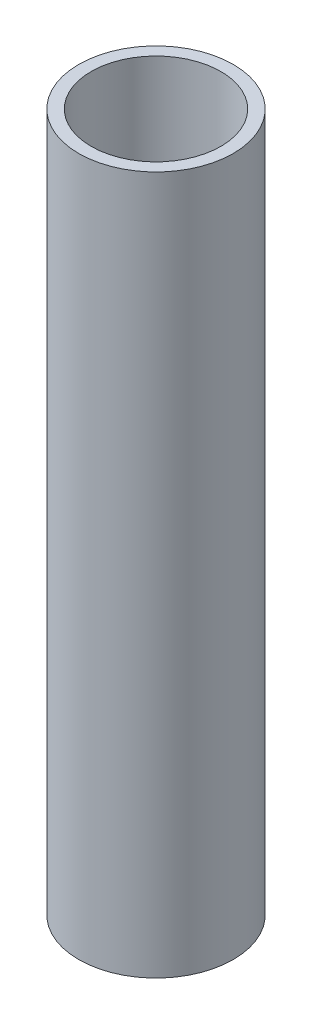
SolidWorks part; units mm, degrees
ref_plane "Front Plane" through (0, 0, 0) normal (0, 0, 1) x (1, 0, 0)
ref_plane "Top Plane" through (0, 0, 0) normal (0, 1, 0) x (1, 0, 0)
ref_plane "Right Plane" through (0, 0, 0) normal (1, 0, 0) x (0, 0, -1)
sketch "Sketch1" plane through (0, 0, 0) normal (0, 1, 0) x (1, 0, 0)
  circle A0 centre (0, 0) radius 12.5
  circle A1 centre (0, 0) radius 10.5
  dimension "D1" = 25
  dimension "D2" = 21
extrude "Boss-Extrude1" add sketch "Sketch1" along normal blind 113
equation "\"cf_tube_outer_diameter\"= 25mm"
equation "\"cf_tube_inner_diameter\" = 21mm"
equation "\"mid_plate_mid_to_top\" = 100mm"
equation "\"mid_plate_mid_to_bottom\" = 30mm"
equation "\"mid_plate_horizontal_spacing\"=250mm"
equation "\"cf_plate_thickness\" =3mm"
equation "\"mid_tube_length\" = 500mm"
equation "\"D1@Sketch1\"=\"cf_tube_outer_diameter\""
equation "\"D2@Sketch1\"=\"cf_tube_inner_diameter\""
